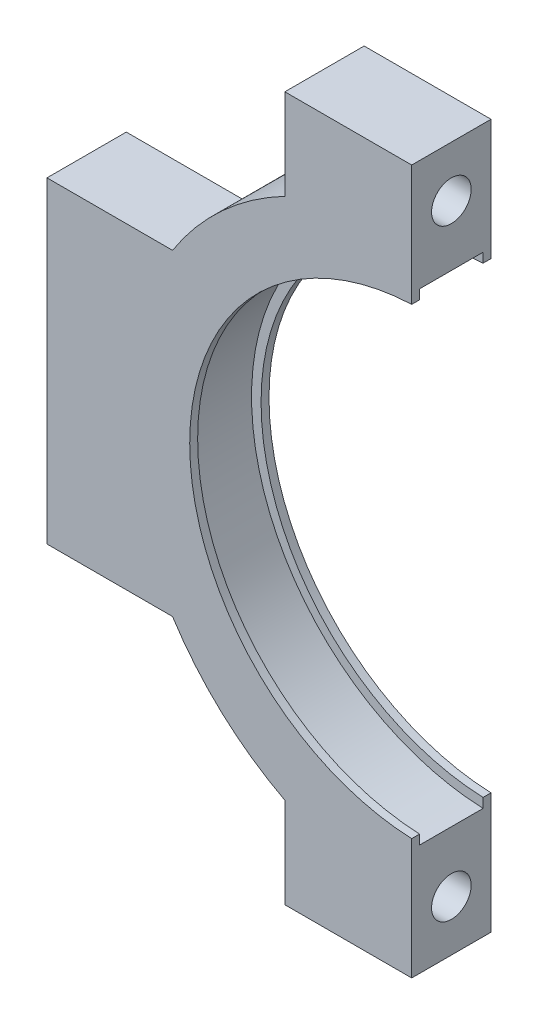
SolidWorks part; units mm, degrees
ref_plane "Front Plane" through (0, 0, 0) normal (0, 0, 1) x (1, 0, 0)
ref_plane "Top Plane" through (0, 0, 0) normal (0, 1, 0) x (1, 0, 0)
ref_plane "Right Plane" through (0, 0, 0) normal (1, 0, 0) x (0, 0, -1)
sketch "Sketch1" plane through (0, 0, 0) normal (0, 0, 1) x (1, 0, 0)
  line L6 (0, 0) -> (50000, 0) construction
  line L7 (0, 0) -> (0, 50000) construction
  line L8 (-3, 111) -> (-43, 111)
  line L9 (-3, -111) -> (-43, -111)
  line L10 (-43, 111) -> (-43, 82.4621)
  line L11 (-43, -111) -> (-43, -82.4621)
  line L12 (-3, 111) -> (-3, 72.9383)
  line L13 (-3, -111) -> (-3, -72.9383)
  arc A2 (-3, 72.9383) -> (-3, -72.9383) centre (0, 0) ccw
  arc A3 (-3, 75.9408) -> (-3, -75.9408) centre (0, 0) ccw
  arc A4 (-3, 92.9516) -> (-3, -92.9516) centre (0, 0) ccw
  dimension "D1" = 73
  dimension "D2" = 76
  dimension "D3" = 93
  dimension "D4" = 40
  dimension "D5" = 3
  dimension "D6" = 222
extrude "Boss-Extrude1" add sketch "Sketch1" along normal mid plane 25 contours L12 A4 L13 A3 | A4 L12 L8 L10 | A4 L11 L9 L13 region at (-24.5949, 99.9389, 0) region at (-5.0654, 84.4462, 0) region at (-24.5949, -99.9389, 0)
extrude "Boss-Extrude2" add sketch "Sketch1<3>" along normal blind 2.5 from offset 10 contours L12 A3 L13 A2 region at (-4.6851, 74.4395, 0)
sketch "Sketch1<3>" plane through (0, 0, 0) normal (0, 0, 1) x (1, 0, 0) same geometry as "Sketch1"
hole_wizard "Ø12.0mm Dowel Hole1" positions "Sketch3" profile "Sketch4" hole size "Ø12.0" standard "ISO" end condition through all
sketch "Sketch3" plane through (-3, 0, 0) normal (1, 0, 0) x (0, 0, -1)
  line L0 (0, 0) -> (54.4803, 0) construction
  line L1 (0, 0) -> (0, 95) construction
  point P0 (0, 95)
  point P2 (0, -95)
  dimension "D1" = 190
sketch "Sketch4" plane through (-3, 95, 0) normal (0, 1, 0) x (0, 0, -1)
  line L0 (0, 0) -> (0, 90)
  line L1 (0, 90) -> (6.25, 90)
  line L2 (6.25, 90) -> (6.25, 0)
  line L5 (6.25, 0) -> (0, 0)
  line L11 (0, -6.35) -> (0, 107.95) construction
  dimension "Thru Hole Dia." = 12.5
  dimension "Thru Hole Depth" = 90
mirror "Mirror2" about plane through (0, 0, 0) normal (0, 0, 1) of "Boss-Extrude2"
sketch "Sketch10" plane through (0, 0, 0) normal (0, 0, 1) x (1, 0, 0)
  line L0 (-78.4156, 50) -> (-118, 50)
  line L1 (-118, 50) -> (-118, -50)
  line L2 (-118, -50) -> (-78.4156, -50)
  line L3 (0, 0) -> (-52.779, 0) construction
  line L4 (-43, -111) -> (-43, -82.4621) construction
  arc A0 (-43, 82.4621) -> (-43, -82.4621) centre (0, 0) ccw construction
  arc A1 (-78.4156, 50) -> (-78.4156, -50) centre (0, 0) ccw
  dimension "D1" = 100
  dimension "D2" = 75
extrude "Boss-Extrude3" add sketch "Sketch10" along normal mid plane 25 contours L1 L2 A1 L0
hole_wizard "Ø8.0mm Dowel Hole1" positions "Sketch11" profile "Sketch13" hole size "Ø8.0" standard "ISO"
sketch "Sketch11" plane through (-118, 0, 0) normal (-1, 0, 0) x (0, 0, 1)
  line L0 (0, 0) -> (31.5412, 0) construction
  point P0 (0, 35)
  point P2 (0, -35)
  point P9 (0, 0)
  point P10 (0, 0)
  point P11 (0, 0)
  dimension "D1" = 70
sketch "Sketch13" plane through (-118, 35, 0) normal (0, 1, 0) x (0, 0, 1)
  line L0 (0, 0) -> (0, 30)
  line L1 (0, 30) -> (4, 30)
  line L2 (4, 30) -> (4, 0)
  line L5 (4, 0) -> (0, 0)
  line L10 (0, 30) -> (-4, 30) construction
  line L11 (0, -6.35) -> (0, 107.95) construction
  dimension "Hole Dia." = 8
  dimension "Hole Depth" = 30
  dimension "Drill Angle" = 180
thread "Thread1" pitch 1 method cut trim with start face yes profile "Thread Profile1" start angle 0, offset 2, length 27, pitch 1, diameter 8
ref_plane "Plane1" through (-120, -35, -4) normal (0, 1, 0) x (0, 0, 1)
sketch "Thread Profile1" plane through (-120, -35, -4) normal (0, 1, 0) x (0, 0, 1)
  line L0 (0, 0) -> (0, 1) construction
  line L11 (0, 0) -> (0, 0.875)
  line L12 (0, 0.875) -> (-0.5413, 0.5625)
  line L13 (-0.5413, 0.5625) -> (-0.5413, 0.3125)
  line L15 (-0.5413, 0.3125) -> (0, 0)
  line L17 (-0.5413, 0.4375) -> (0, 0.4375) construction
  point P2 (0, 0)
  dimension "Pitch" = 1
  dimension "Profile_Angle" = 60
  dimension "Profile_Land" = 0.25
  dimension "Profile_Height" = 0.5413
thread "Thread2" pitch 1 method cut trim with start face yes profile "Thread Profile2" start angle 0, offset 2, length 27, pitch 1, diameter 8
ref_plane "Plane2" through (-120, 35, -4) normal (0, 1, 0) x (0, 0, 1)
sketch "Thread Profile2" plane through (-120, 35, -4) normal (0, 1, 0) x (0, 0, 1)
  line L0 (0, 0) -> (0, 1) construction
  line L11 (0, 0) -> (0, 0.875)
  line L12 (0, 0.875) -> (-0.5413, 0.5625)
  line L13 (-0.5413, 0.5625) -> (-0.5413, 0.3125)
  line L15 (-0.5413, 0.3125) -> (0, 0)
  line L17 (-0.5413, 0.4375) -> (0, 0.4375) construction
  point P2 (0, 0)
  dimension "Pitch" = 1
  dimension "Profile_Angle" = 60
  dimension "Profile_Land" = 0.25
  dimension "Profile_Height" = 0.5413
sketch "Sketch24" plane through (-43, 0, 0) normal (-1, 0, 0) x (0, 0, 1)
  line L0 (0, 86) -> (0, 95) construction
  line L1 (-2, 86) -> (-2, 89.0786)
  line L2 (2, 86) -> (2, 89.0786)
  line L3 (0, 20.5811) -> (0, 0) construction
  line L4 (0, 0) -> (25.7181, 0) construction
  line L5 (-2, -86) -> (-2, -89.0786)
  line L6 (2, -86) -> (2, -89.0786)
  arc A0 (-2, 86) -> (2, 86) centre (0, 86) ccw
  circle A1 centre (0, 95) radius 6.25 construction
  arc A2 (-2, 89.0786) -> (2, 89.0786) centre (0, 95) ccw
  arc A3 (-2, -89.0786) -> (2, -89.0786) centre (0, -95) cw
  arc A4 (-2, -86) -> (2, -86) centre (0, -86) cw
  dimension "D1" = 4
  dimension "D2" = 9
extrude "Cut-Extrude3" cut sketch "Sketch24" against normal blind 6
